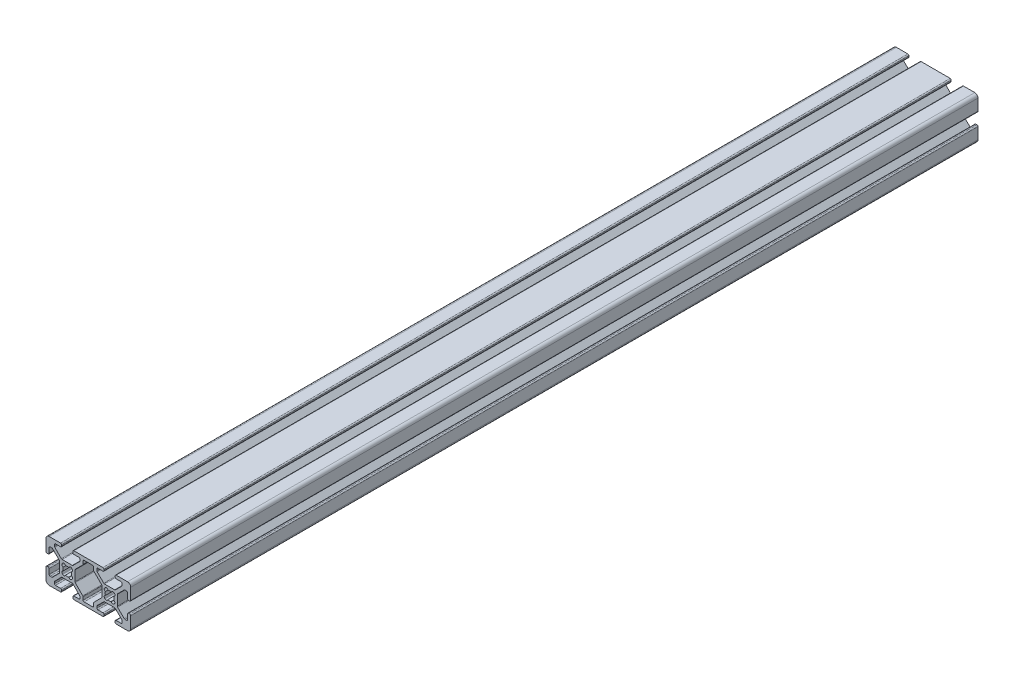
SolidWorks part; units mm, degrees
material "6105-T5 Aluminum"
ref_plane "Front Plane" through (0, 0, 0) normal (0, 0, 1) x (1, 0, 0)
ref_plane "Top Plane" through (0, 0, 0) normal (0, 1, 0) x (1, 0, 0)
ref_plane "Right Plane" through (0, 0, 0) normal (1, 0, 0) x (0, 0, -1)
sketch "Sketch1" plane through (0, 0, 0) normal (0, 0, 1) x (1, 0, 0)
  line L0 (-2.1249, -2.3045) -> (-2.3045, -2.1249)
  line L1 (-2.3045, 2.1249) -> (-2.1249, 2.3045)
  line L2 (2.1249, 2.3045) -> (2.3045, 2.1249)
  line L3 (2.3045, -2.1249) -> (2.1249, -2.3045)
  line L4 (-12.505, -7.992) -> (-12.505, -6.6448)
  line L5 (-12.6538, -6.2856) -> (-16.1962, -2.7431)
  line L6 (-16.345, -2.3839) -> (-16.345, 2.3839)
  line L7 (-16.1962, 2.7431) -> (-12.6538, 6.2856)
  line L8 (-12.505, 6.6448) -> (-12.505, 7.992)
  line L9 (-11.997, 8.5) -> (-8.003, 8.5)
  line L10 (-7.495, 7.992) -> (-7.495, 6.6448)
  line L11 (-7.3462, 6.2856) -> (-3.8038, 2.7431)
  line L12 (-3.655, 2.3839) -> (-3.655, -2.3839)
  line L13 (-3.8038, -2.7431) -> (-7.3462, -6.2856)
  line L14 (-7.495, -6.6448) -> (-7.495, -7.992)
  line L15 (-8.003, -8.5) -> (-11.997, -8.5)
  line L16 (-22.1249, -2.3045) -> (-22.3045, -2.1249)
  line L17 (-22.3045, 2.1249) -> (-22.1249, 2.3045)
  line L18 (-17.8751, 2.3045) -> (-17.6955, 2.1249)
  line L19 (-17.6955, -2.1249) -> (-17.8751, -2.3045)
  line L20 (-22.3839, -3.655) -> (-17.6161, -3.655)
  line L21 (-17.2569, -3.8038) -> (-14.1538, -6.9069)
  line L22 (-14.005, -7.2661) -> (-14.005, -7.992)
  line L23 (-14.513, -8.5) -> (-16.862, -8.5)
  line L24 (-17.37, -9.008) -> (-17.37, -9.492)
  line L25 (-16.862, -10) -> (-3.138, -10)
  line L26 (-2.63, -9.492) -> (-2.63, -9.008)
  line L27 (-3.138, -8.5) -> (-5.487, -8.5)
  line L28 (-5.995, -7.992) -> (-5.995, -7.2661)
  line L29 (-5.8462, -6.9069) -> (-2.7431, -3.8038)
  line L30 (-2.3839, -3.655) -> (2.3839, -3.655)
  line L31 (2.7431, -3.8038) -> (5.8462, -6.9069)
  line L32 (5.995, -7.2661) -> (5.995, -7.992)
  line L33 (5.487, -8.5) -> (3.138, -8.5)
  line L34 (2.63, -9.008) -> (2.63, -9.492)
  line L35 (3.138, -10) -> (8.5, -10)
  line L36 (10, -8.5) -> (10, -3.138)
  line L37 (9.492, -2.63) -> (9.008, -2.63)
  line L38 (8.5, -3.138) -> (8.5, -5.487)
  line L39 (7.992, -5.995) -> (7.2661, -5.995)
  line L40 (6.9069, -5.8462) -> (3.8038, -2.7431)
  line L41 (3.655, -2.3839) -> (3.655, 2.3839)
  line L42 (3.8038, 2.7431) -> (6.9069, 5.8462)
  line L43 (7.2661, 5.995) -> (7.992, 5.995)
  line L44 (8.5, 5.487) -> (8.5, 3.138)
  line L45 (9.008, 2.63) -> (9.492, 2.63)
  line L46 (10, 3.138) -> (10, 8.5)
  line L47 (8.5, 10) -> (3.138, 10)
  line L48 (2.63, 9.492) -> (2.63, 9.008)
  line L49 (3.138, 8.5) -> (5.487, 8.5)
  line L50 (5.995, 7.992) -> (5.995, 7.2661)
  line L51 (5.8462, 6.9069) -> (2.7431, 3.8038)
  line L52 (2.3839, 3.655) -> (-2.3839, 3.655)
  line L53 (-2.7431, 3.8038) -> (-5.8462, 6.9069)
  line L54 (-5.995, 7.2661) -> (-5.995, 7.992)
  line L55 (-5.487, 8.5) -> (-3.138, 8.5)
  line L56 (-2.63, 9.008) -> (-2.63, 9.492)
  line L57 (-3.138, 10) -> (-16.862, 10)
  line L58 (-17.37, 9.492) -> (-17.37, 9.008)
  line L59 (-16.862, 8.5) -> (-14.513, 8.5)
  line L60 (-14.005, 7.992) -> (-14.005, 7.2661)
  line L61 (-14.1538, 6.9069) -> (-17.2569, 3.8038)
  line L62 (-17.6161, 3.655) -> (-22.3839, 3.655)
  line L63 (-22.7431, 3.8038) -> (-25.8462, 6.9069)
  line L64 (-25.995, 7.2661) -> (-25.995, 7.992)
  line L65 (-25.487, 8.5) -> (-23.138, 8.5)
  line L66 (-22.63, 9.008) -> (-22.63, 9.492)
  line L67 (-23.138, 10) -> (-28.5, 10)
  line L68 (-30, 8.5) -> (-30, 3.138)
  line L69 (-29.492, 2.63) -> (-29.008, 2.63)
  line L70 (-28.5, 3.138) -> (-28.5, 5.487)
  line L71 (-27.992, 5.995) -> (-27.2661, 5.995)
  line L72 (-26.9069, 5.8462) -> (-23.8038, 2.7431)
  line L73 (-23.655, 2.3839) -> (-23.655, -2.3839)
  line L74 (-23.8038, -2.7431) -> (-26.9069, -5.8462)
  line L75 (-27.2661, -5.995) -> (-27.992, -5.995)
  line L76 (-28.5, -5.487) -> (-28.5, -3.138)
  line L77 (-29.008, -2.63) -> (-29.492, -2.63)
  line L78 (-30, -3.138) -> (-30, -8.5)
  line L79 (-28.5, -10) -> (-23.138, -10)
  line L80 (-22.63, -9.492) -> (-22.63, -9.008)
  line L81 (-23.138, -8.5) -> (-25.487, -8.5)
  line L82 (-25.995, -7.992) -> (-25.995, -7.2661)
  line L83 (-25.8462, -6.9069) -> (-22.7431, -3.8038)
  arc A0 (-1.9351, -0.804) -> (-2.3045, -2.1249) centre (-1.748, -1.5684) ccw
  arc A1 (-1.9351, 0.804) -> (-1.9351, -0.804) centre (0, 0) ccw
  arc A2 (-2.3045, 2.1249) -> (-1.9351, 0.804) centre (-1.748, 1.5684) ccw
  arc A3 (-0.804, 1.9351) -> (-2.1249, 2.3045) centre (-1.5684, 1.748) ccw
  arc A4 (0.804, 1.9351) -> (-0.804, 1.9351) centre (0, 0) ccw
  arc A5 (2.1249, 2.3045) -> (0.804, 1.9351) centre (1.5684, 1.748) ccw
  arc A6 (1.9351, 0.804) -> (2.3045, 2.1249) centre (1.748, 1.5684) ccw
  arc A7 (1.9351, -0.804) -> (1.9351, 0.804) centre (0, 0) ccw
  arc A8 (2.3045, -2.1249) -> (1.9351, -0.804) centre (1.748, -1.5684) ccw
  arc A9 (0.804, -1.9351) -> (2.1249, -2.3045) centre (1.5684, -1.748) ccw
  arc A10 (-0.804, -1.9351) -> (0.804, -1.9351) centre (0, 0) ccw
  arc A11 (-2.1249, -2.3045) -> (-0.804, -1.9351) centre (-1.5684, -1.748) ccw
  arc A12 (-12.505, -7.992) -> (-11.997, -8.5) centre (-11.997, -7.992) ccw
  arc A13 (-12.505, -6.6448) -> (-12.6538, -6.2856) centre (-13.013, -6.6448) ccw
  arc A14 (-16.345, -2.3839) -> (-16.1962, -2.7431) centre (-15.837, -2.3839) ccw
  arc A15 (-16.1962, 2.7431) -> (-16.345, 2.3839) centre (-15.837, 2.3839) ccw
  arc A16 (-12.6538, 6.2856) -> (-12.505, 6.6448) centre (-13.013, 6.6448) ccw
  arc A17 (-11.997, 8.5) -> (-12.505, 7.992) centre (-11.997, 7.992) ccw
  arc A18 (-7.495, 7.992) -> (-8.003, 8.5) centre (-8.003, 7.992) ccw
  arc A19 (-7.495, 6.6448) -> (-7.3462, 6.2856) centre (-6.987, 6.6448) ccw
  arc A20 (-3.655, 2.3839) -> (-3.8038, 2.7431) centre (-4.163, 2.3839) ccw
  arc A21 (-3.8038, -2.7431) -> (-3.655, -2.3839) centre (-4.163, -2.3839) ccw
  arc A22 (-7.3462, -6.2856) -> (-7.495, -6.6448) centre (-6.987, -6.6448) ccw
  arc A23 (-8.003, -8.5) -> (-7.495, -7.992) centre (-8.003, -7.992) ccw
  arc A24 (-21.9351, -0.804) -> (-22.3045, -2.1249) centre (-21.748, -1.5684) ccw
  arc A25 (-21.9351, 0.804) -> (-21.9351, -0.804) centre (-20, 0) ccw
  arc A26 (-22.3045, 2.1249) -> (-21.9351, 0.804) centre (-21.748, 1.5684) ccw
  arc A27 (-20.804, 1.9351) -> (-22.1249, 2.3045) centre (-21.5684, 1.748) ccw
  arc A28 (-19.196, 1.9351) -> (-20.804, 1.9351) centre (-20, 0) ccw
  arc A29 (-17.8751, 2.3045) -> (-19.196, 1.9351) centre (-18.4316, 1.748) ccw
  arc A30 (-18.0649, 0.804) -> (-17.6955, 2.1249) centre (-18.252, 1.5684) ccw
  arc A31 (-18.0649, -0.804) -> (-18.0649, 0.804) centre (-20, 0) ccw
  arc A32 (-17.6955, -2.1249) -> (-18.0649, -0.804) centre (-18.252, -1.5684) ccw
  arc A33 (-19.196, -1.9351) -> (-17.8751, -2.3045) centre (-18.4316, -1.748) ccw
  arc A34 (-20.804, -1.9351) -> (-19.196, -1.9351) centre (-20, 0) ccw
  arc A35 (-22.1249, -2.3045) -> (-20.804, -1.9351) centre (-21.5684, -1.748) ccw
  arc A36 (-22.3839, -3.655) -> (-22.7431, -3.8038) centre (-22.3839, -4.163) ccw
  arc A37 (-17.2569, -3.8038) -> (-17.6161, -3.655) centre (-17.6161, -4.163) ccw
  arc A38 (-14.005, -7.2661) -> (-14.1538, -6.9069) centre (-14.513, -7.2661) ccw
  arc A39 (-14.513, -8.5) -> (-14.005, -7.992) centre (-14.513, -7.992) ccw
  arc A40 (-16.862, -8.5) -> (-17.37, -9.008) centre (-16.862, -9.008) ccw
  arc A41 (-17.37, -9.492) -> (-16.862, -10) centre (-16.862, -9.492) ccw
  arc A42 (-3.138, -10) -> (-2.63, -9.492) centre (-3.138, -9.492) ccw
  arc A43 (-2.63, -9.008) -> (-3.138, -8.5) centre (-3.138, -9.008) ccw
  arc A44 (-5.995, -7.992) -> (-5.487, -8.5) centre (-5.487, -7.992) ccw
  arc A45 (-5.8462, -6.9069) -> (-5.995, -7.2661) centre (-5.487, -7.2661) ccw
  arc A46 (-2.3839, -3.655) -> (-2.7431, -3.8038) centre (-2.3839, -4.163) ccw
  arc A47 (2.7431, -3.8038) -> (2.3839, -3.655) centre (2.3839, -4.163) ccw
  arc A48 (5.995, -7.2661) -> (5.8462, -6.9069) centre (5.487, -7.2661) ccw
  arc A49 (5.487, -8.5) -> (5.995, -7.992) centre (5.487, -7.992) ccw
  arc A50 (3.138, -8.5) -> (2.63, -9.008) centre (3.138, -9.008) ccw
  arc A51 (2.63, -9.492) -> (3.138, -10) centre (3.138, -9.492) ccw
  arc A52 (8.5, -10) -> (10, -8.5) centre (8.5, -8.5) ccw
  arc A53 (10, -3.138) -> (9.492, -2.63) centre (9.492, -3.138) ccw
  arc A54 (9.008, -2.63) -> (8.5, -3.138) centre (9.008, -3.138) ccw
  arc A55 (7.992, -5.995) -> (8.5, -5.487) centre (7.992, -5.487) ccw
  arc A56 (6.9069, -5.8462) -> (7.2661, -5.995) centre (7.2661, -5.487) ccw
  arc A57 (3.655, -2.3839) -> (3.8038, -2.7431) centre (4.163, -2.3839) ccw
  arc A58 (3.8038, 2.7431) -> (3.655, 2.3839) centre (4.163, 2.3839) ccw
  arc A59 (7.2661, 5.995) -> (6.9069, 5.8462) centre (7.2661, 5.487) ccw
  arc A60 (8.5, 5.487) -> (7.992, 5.995) centre (7.992, 5.487) ccw
  arc A61 (8.5, 3.138) -> (9.008, 2.63) centre (9.008, 3.138) ccw
  arc A62 (9.492, 2.63) -> (10, 3.138) centre (9.492, 3.138) ccw
  arc A63 (10, 8.5) -> (8.5, 10) centre (8.5, 8.5) ccw
  arc A64 (3.138, 10) -> (2.63, 9.492) centre (3.138, 9.492) ccw
  arc A65 (2.63, 9.008) -> (3.138, 8.5) centre (3.138, 9.008) ccw
  arc A66 (5.995, 7.992) -> (5.487, 8.5) centre (5.487, 7.992) ccw
  arc A67 (5.8462, 6.9069) -> (5.995, 7.2661) centre (5.487, 7.2661) ccw
  arc A68 (2.3839, 3.655) -> (2.7431, 3.8038) centre (2.3839, 4.163) ccw
  arc A69 (-2.7431, 3.8038) -> (-2.3839, 3.655) centre (-2.3839, 4.163) ccw
  arc A70 (-5.995, 7.2661) -> (-5.8462, 6.9069) centre (-5.487, 7.2661) ccw
  arc A71 (-5.487, 8.5) -> (-5.995, 7.992) centre (-5.487, 7.992) ccw
  arc A72 (-3.138, 8.5) -> (-2.63, 9.008) centre (-3.138, 9.008) ccw
  arc A73 (-2.63, 9.492) -> (-3.138, 10) centre (-3.138, 9.492) ccw
  arc A74 (-16.862, 10) -> (-17.37, 9.492) centre (-16.862, 9.492) ccw
  arc A75 (-17.37, 9.008) -> (-16.862, 8.5) centre (-16.862, 9.008) ccw
  arc A76 (-14.005, 7.992) -> (-14.513, 8.5) centre (-14.513, 7.992) ccw
  arc A77 (-14.1538, 6.9069) -> (-14.005, 7.2661) centre (-14.513, 7.2661) ccw
  arc A78 (-17.6161, 3.655) -> (-17.2569, 3.8038) centre (-17.6161, 4.163) ccw
  arc A79 (-22.7431, 3.8038) -> (-22.3839, 3.655) centre (-22.3839, 4.163) ccw
  arc A80 (-25.995, 7.2661) -> (-25.8462, 6.9069) centre (-25.487, 7.2661) ccw
  arc A81 (-25.487, 8.5) -> (-25.995, 7.992) centre (-25.487, 7.992) ccw
  arc A82 (-23.138, 8.5) -> (-22.63, 9.008) centre (-23.138, 9.008) ccw
  arc A83 (-22.63, 9.492) -> (-23.138, 10) centre (-23.138, 9.492) ccw
  arc A84 (-28.5, 10) -> (-30, 8.5) centre (-28.5, 8.5) ccw
  arc A85 (-30, 3.138) -> (-29.492, 2.63) centre (-29.492, 3.138) ccw
  arc A86 (-29.008, 2.63) -> (-28.5, 3.138) centre (-29.008, 3.138) ccw
  arc A87 (-27.992, 5.995) -> (-28.5, 5.487) centre (-27.992, 5.487) ccw
  arc A88 (-26.9069, 5.8462) -> (-27.2661, 5.995) centre (-27.2661, 5.487) ccw
  arc A89 (-23.655, 2.3839) -> (-23.8038, 2.7431) centre (-24.163, 2.3839) ccw
  arc A90 (-23.8038, -2.7431) -> (-23.655, -2.3839) centre (-24.163, -2.3839) ccw
  arc A91 (-27.2661, -5.995) -> (-26.9069, -5.8462) centre (-27.2661, -5.487) ccw
  arc A92 (-28.5, -5.487) -> (-27.992, -5.995) centre (-27.992, -5.487) ccw
  arc A93 (-28.5, -3.138) -> (-29.008, -2.63) centre (-29.008, -3.138) ccw
  arc A94 (-29.492, -2.63) -> (-30, -3.138) centre (-29.492, -3.138) ccw
  arc A95 (-30, -8.5) -> (-28.5, -10) centre (-28.5, -8.5) ccw
  arc A96 (-23.138, -10) -> (-22.63, -9.492) centre (-23.138, -9.492) ccw
  arc A97 (-22.63, -9.008) -> (-23.138, -8.5) centre (-23.138, -9.008) ccw
  arc A98 (-25.995, -7.992) -> (-25.487, -8.5) centre (-25.487, -7.992) ccw
  arc A99 (-25.8462, -6.9069) -> (-25.995, -7.2661) centre (-25.487, -7.2661) ccw
extrude "Extrude1" add sketch "Sketch1" against normal blind 400
